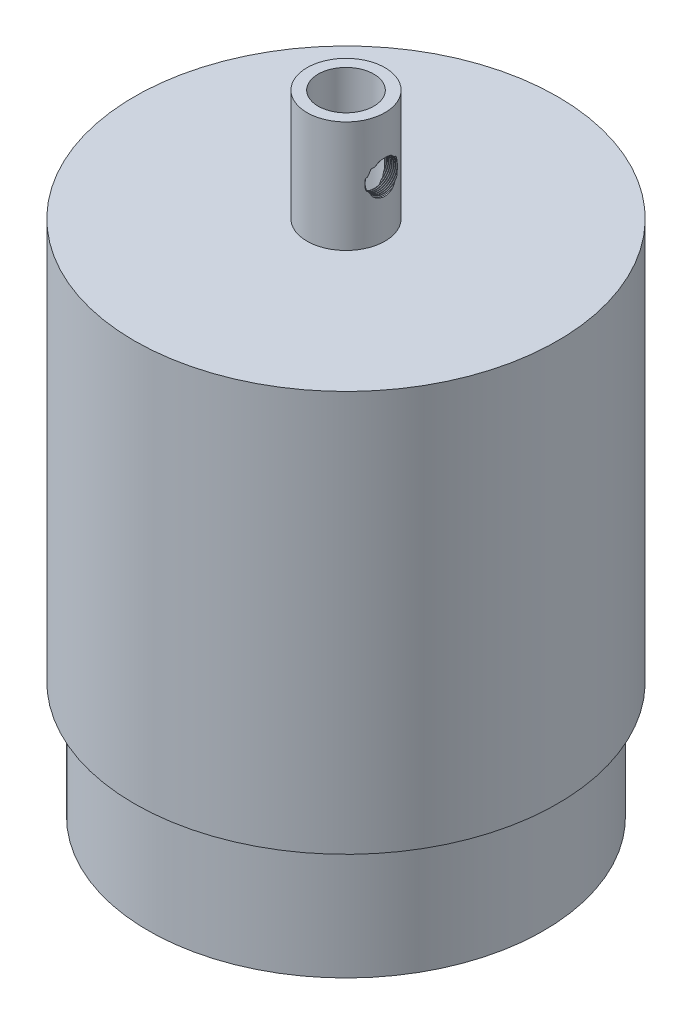
SolidWorks part; units mm, degrees
material "ASTM A36 Steel"
ref_plane "Front Plane" through (0, 0, 0) normal (0, 0, 1) x (1, 0, 0)
ref_plane "Top Plane" through (0, 0, 0) normal (0, 1, 0) x (1, 0, 0)
ref_plane "Right Plane" through (0, 0, 0) normal (1, 0, 0) x (0, 0, -1)
sketch "Sketch1" plane through (0, 0, 0) normal (0, 1, 0) x (1, 0, 0)
  circle A0 centre (0, 0) radius 35
  circle A1 centre (0, 0) radius 38
  dimension "D1" = 3
  dimension "D2" = 70
extrude "Boss-Extrude1" add sketch "Sketch1" along normal blind 90
sketch "Sketch2" plane through (0, 0, 0) normal (0, -1, 0) x (1, 0, 0)
  circle A0 centre (0, 0) radius 38
  circle A1 centre (0, 0) radius 37
  dimension "D1" = 1
extrude "Cut-Extrude1" cut sketch "Sketch2" against normal blind 21
sketch "Sketch3" plane through (0, 90, 0) normal (0, 1, 0) x (1, 0, 0)
  circle A0 centre (0, 0) radius 38
extrude "Boss-Extrude2" add sketch "Sketch3" along normal blind 3
sketch "Sketch4" plane through (0, 93, 0) normal (0, 1, 0) x (1, 0, 0)
  circle A0 centre (0, 0) radius 5
  circle A1 centre (0, 0) radius 7
  dimension "D1" = 2
extrude "Boss-Extrude3" add sketch "Sketch4" along normal blind 20
sketch "Sketch5" plane through (0, 93, 0) normal (0, 1, 0) x (1, 0, 0)
  circle A0 centre (0, 0) radius 5
extrude "Cut-Extrude2" cut sketch "Sketch5" against normal blind 20
ref_plane "Plane1" through (7, 0, 0) normal (1, 0, 0) x (0, 0, -1)
sketch "Sketch6" plane through (7, 0, 0) normal (1, 0, 0) x (0, 0, -1)
  line L0 (0, 113) -> (0, 93)
  line L1 (7, 113) -> (-7, 113) construction
  line L2 (38, 93) -> (-38, 93) construction
  circle A0 centre (0, 103) radius 3
extrude "Cut-Extrude3" cut sketch "Sketch6" against normal blind 3 contours L0 A0 | L0 A0 region at (7, 103, -1.2732) region at (7, 103, 1.2732)
thread "Thread1" pitch 0.3175 method extrude profile "Thread Profile1" start angle 0, offset 0.0001, length 0, pitch 0.3175, diameter 6
ref_plane "Plane2" through (6.9999, 103, 3) normal (0, -1, 0) x (0, 0, 1)
sketch "Thread Profile1" plane through (6.9999, 103, 3) normal (0, -1, 0) x (0, 0, 1)
  line L0 (0, 0) -> (0, 0.3175) construction
  line L11 (0, 0) -> (0, 0.2778)
  line L12 (0, 0.2778) -> (-0.1719, 0.1786)
  line L13 (-0.1719, 0.1786) -> (-0.1719, 0.0992)
  line L15 (-0.1719, 0.0992) -> (0, 0)
  line L17 (-0.1719, 0.1389) -> (0, 0.1389) construction
  point P2 (0, 0)
  dimension "Pitch" = 0.3175
  dimension "Profile_Angle" = 60
  dimension "Profile_Land" = 0.0794
  dimension "Profile_Height" = 0.1719
sketch "Sketch9" plane through (0, 113, 0) normal (0, 1, 0) x (1, 0, 0)
  circle A0 centre (0, 0) radius 5
extrude "Cut-Extrude5" cut sketch "Sketch9" against normal blind 50
sketch "Sketch10" plane through (0, 113, 0) normal (0, 1, 0) x (1, 0, 0)
  circle A0 centre (0, 0) radius 7
  circle A1 centre (0, 0) radius 10.922
extrude "Cut-Extrude6" cut sketch "Sketch10" against normal blind 20
sketch "Sketch11" plane through (0, 0, 0) normal (0, -1, 0) x (1, 0, 0)
  circle A0 centre (0, 0) radius 35.5
  circle A1 centre (0, 0) radius 42.7399
extrude "Cut-Extrude7" cut sketch "Sketch11" against normal blind 21
